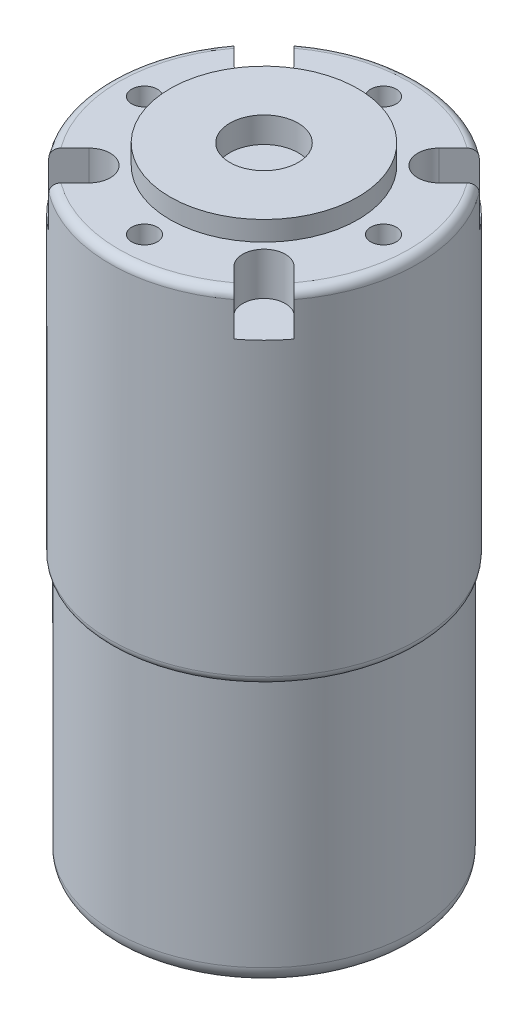
SolidWorks part; units mm, degrees
ref_plane "前视基准面" through (0, 0, 0) normal (0, 0, 1) x (1, 0, 0)
ref_plane "上视基准面" through (0, 0, 0) normal (0, 1, 0) x (1, 0, 0)
ref_plane "右视基准面" through (0, 0, 0) normal (1, 0, 0) x (0, 0, -1)
sketch "Sketch1" plane through (0, 0, 0) normal (0, 1, 0) x (1, 0, 0)
  circle A0 centre (0, 0) radius 17.5
  dimension "D1" = 35
extrude "Boss-Extrude1" add sketch "Sketch1" along normal blind 31
sketch "Sketch2" plane through (0, 31, 0) normal (0, 1, 0) x (1, 0, 0)
  circle A0 centre (0, 0) radius 18
  dimension "D1" = 36
extrude "Boss-Extrude2" add sketch "Sketch2" along normal blind 40
fillet "Fillet1" radius 2 1 edges at (0, 0, 17.5)
fillet "Fillet2" radius 1 1 edges at (0, 31, 18)
sketch "Sketch3" plane through (0, 71, 0) normal (0, 1, 0) x (1, 0, 0)
  circle A0 centre (0, 0) radius 11
  dimension "D1" = 22
extrude "Boss-Extrude3" add sketch "Sketch3" along normal blind 2.3
sketch "Sketch4" plane through (0, 73.3, 0) normal (0, 1, 0) x (1, 0, 0)
  circle A0 centre (0, 0) radius 4
  dimension "D1" = 8
extrude "Cut-Extrude1" cut sketch "Sketch4" against normal blind 3
sketch "Sketch5" plane through (0, 71, 0) normal (0, 1, 0) x (1, 0, 0)
  line L0 (-26.329, 0) -> (24.8356, 0) construction
  circle A0 centre (0, 0) radius 14 construction
  circle A1 centre (-14, 0) radius 1.5
  circle A2 centre (0, 14) radius 1.5
  circle A3 centre (14, 0) radius 1.5
  circle A4 centre (0, -14) radius 1.5
  point P16 (0, 0)
  dimension "D1" = 28
  dimension "D2" = 3
  dimension "D3" = 4
extrude "Cut-Extrude2" cut sketch "Sketch5" against normal blind 5
fillet "Fillet3" radius 1 1 edges at (0, 71, 18)
sketch "Sketch6" plane through (0, 71, 0) normal (0, 1, 0) x (1, 0, 0)
  line L0 (-27.9847, 0) -> (24.1213, 0) construction
  line L1 (-19.2476, 19.2476) -> (0, 0) construction
  line L2 (-14.3723, 10.8368) -> (-12.0208, 8.4853)
  line L3 (-10.8368, 14.3723) -> (-8.4853, 12.0208)
  line L4 (14.3723, 10.8368) -> (12.0208, 8.4853)
  line L5 (10.8368, 14.3723) -> (8.4853, 12.0208)
  line L6 (10.8368, -14.3723) -> (8.4853, -12.0208)
  line L7 (14.3723, -10.8368) -> (12.0208, -8.4853)
  line L8 (-14.3723, -10.8368) -> (-12.0208, -8.4853)
  line L9 (-10.8368, -14.3723) -> (-8.4853, -12.0208)
  circle A0 centre (0, 0) radius 14.5 construction
  arc A1 (-12.0208, 8.4853) -> (-8.4853, 12.0208) centre (-10.253, 10.253) ccw
  arc A3 (-10.8368, 14.3723) -> (-14.3723, 10.8368) centre (0, 0) ccw
  arc A4 (8.4853, 12.0208) -> (12.0208, 8.4853) centre (10.253, 10.253) ccw
  arc A5 (14.3723, 10.8368) -> (10.8368, 14.3723) centre (0, 0) ccw
  arc A6 (12.0208, -8.4853) -> (8.4853, -12.0208) centre (10.253, -10.253) ccw
  arc A7 (10.8368, -14.3723) -> (14.3723, -10.8368) centre (0, 0) ccw
  arc A8 (-8.4853, -12.0208) -> (-12.0208, -8.4853) centre (-10.253, -10.253) ccw
  arc A9 (-14.3723, -10.8368) -> (-10.8368, -14.3723) centre (0, 0) ccw
  point P29 (0, 0)
  dimension "D2" = 29
  dimension "D3" = 5
  dimension "D4" = 18
  dimension "D1" = 45
  dimension "D5" = 4
extrude "Cut-Extrude3" cut sketch "Sketch6" against normal blind 5 contours L3 A1 L2 A3 | L4 A4 L5 A5 | L6 A6 L7 A7 | L8 A8 L9 A9
